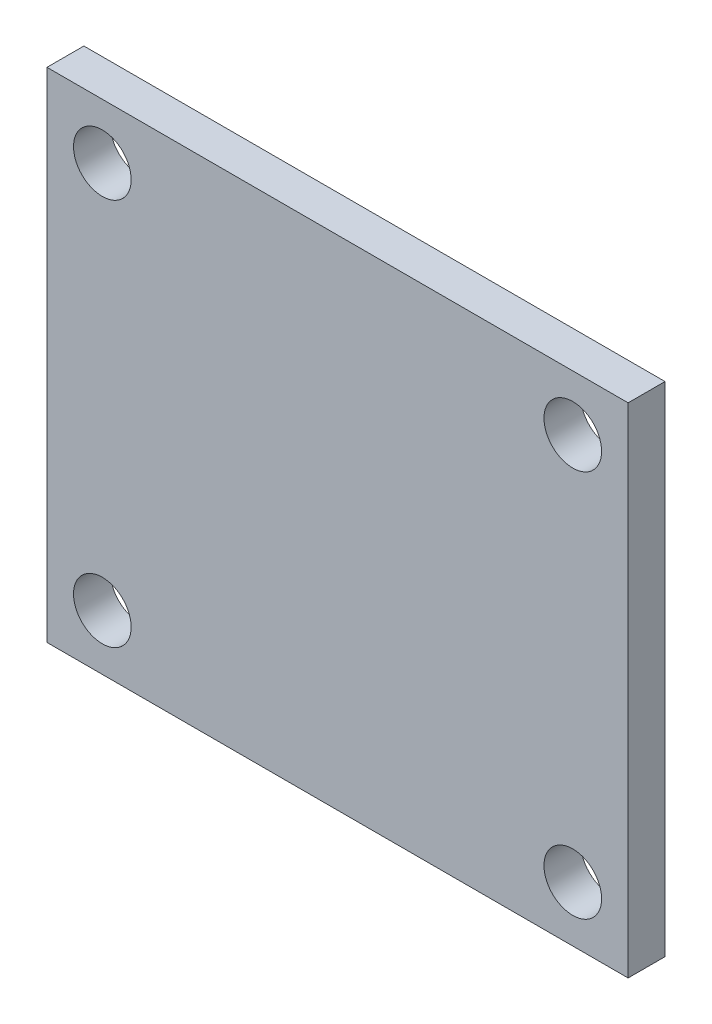
SolidWorks part; units mm, degrees
ref_plane "Front Plane" through (0, 0, 0) normal (0, 0, 1) x (1, 0, 0)
ref_plane "Top Plane" through (0, 0, 0) normal (0, 1, 0) x (1, 0, 0)
ref_plane "Right Plane" through (0, 0, 0) normal (1, 0, 0) x (0, 0, -1)
sketch "Sketch1" plane through (0, 0, 0) normal (0, 0, 1) x (1, 0, 0)
  line L0 (-12.75, -10.5) -> (12.75, 10.5) construction
  line L1 (-15.75, 13.5) -> (15.75, 13.5)
  line L2 (-15.75, 13.5) -> (-15.75, -13.5)
  line L3 (-15.75, -13.5) -> (15.75, -13.5)
  line L4 (15.75, 13.5) -> (15.75, -13.5)
  line L5 (-15.75, 13.5) -> (15.75, -13.5) construction
  line L6 (-15.75, -13.5) -> (15.75, 13.5) construction
  line L8 (-12.75, 10.5) -> (12.75, -10.5) construction
  line L9 (-6, 4) -> (6, 4)
  line L10 (-6, 4) -> (-6, -4)
  line L11 (-6, -4) -> (6, -4)
  line L12 (6, 4) -> (6, -4)
  line L13 (-6, 4) -> (6, -4) construction
  line L14 (-6, -4) -> (6, 4) construction
  circle A0 centre (-12.75, 10.5) radius 1.5625
  circle A1 centre (-12.75, -10.5) radius 1.5625
  circle A2 centre (12.75, 10.5) radius 1.5625
  circle A3 centre (12.75, -10.5) radius 1.5625
  point P0 (0, 0)
  point P14 (0, 0)
  point P15 (0, 0)
  point P20 (0, 0)
  point P21 (0, 0)
  dimension "D3" = 3.125
  dimension "D1" = 31.5
  dimension "D2" = 27
  dimension "D4" = 3
  dimension "D5" = 3
  dimension "D6" = 12
  dimension "D7" = 8
extrude "Boss-Extrude1" add sketch "Sketch1" along normal blind 2 contours L12 L9 L10 L11 | L4 L1 L2 L3 A3 A2 A1 A0 L9 L12 L11 L10 region at (0, 13.0851, 0) region at (0, 0, 0)
extrude "Boss-Extrude2" add sketch "Sketch1<3>" against normal blind 1 contours L12 L9 L10 L11 region at (0, 0, 0)
sketch "Sketch1<3>" plane through (0, 0, 0) normal (0, 0, 1) x (1, 0, 0) same geometry as "Sketch1"
sketch "Sketch2" plane through (0, 0, -1) normal (0, 0, -1) x (-1, 0, 0)
  circle A0 centre (0, 0) radius 1.0034
extrude "Boss-Extrude3" add sketch "Sketch2" along normal blind 0.1
